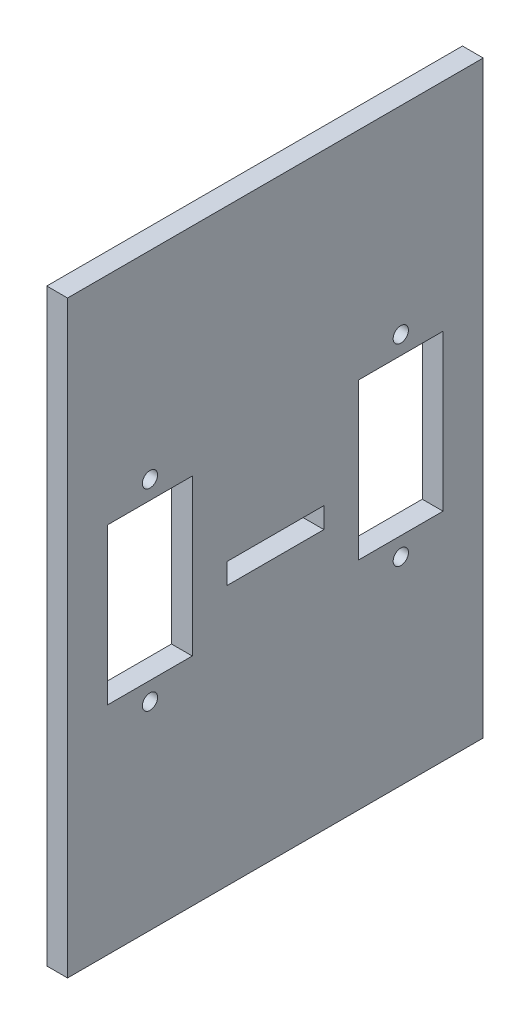
SolidWorks part; units mm, degrees
ref_plane "Front Plane" through (0, 0, 0) normal (0, 0, 1) x (1, 0, 0)
ref_plane "Top Plane" through (0, 0, 0) normal (0, 1, 0) x (1, 0, 0)
ref_plane "Right Plane" through (0, 0, 0) normal (1, 0, 0) x (0, 0, -1)
sketch "Sketch1" plane through (0, 0, 0) normal (1, 0, 0) x (0, 0, -1)
  line L0 (30, 0) -> (-30, 0) construction
  line L1 (-30, -42.5) -> (30, -42.5)
  line L2 (-30, -42.5) -> (-30, 42.5)
  line L3 (-30, 42.5) -> (30, 42.5)
  line L4 (30, -42.5) -> (30, 42.5)
  line L5 (-30, -42.5) -> (30, 42.5) construction
  line L6 (-30, 42.5) -> (30, -42.5) construction
  line L7 (0, 0) -> (12, 0) construction
  line L8 (24.2, -11.25) -> (12, -11.25)
  line L9 (24.2, -11.25) -> (24.2, 11.25)
  line L10 (24.2, 11.25) -> (12, 11.25)
  line L11 (12, -11.25) -> (12, 11.25)
  line L12 (18.1, 11.25) -> (18.1, 13.9) construction
  line L13 (0, 42.5) -> (0, -42.5) construction
  line L14 (-24.2, -11.25) -> (-12, -11.25)
  line L15 (-12, -11.25) -> (-12, 11.25)
  line L16 (-24.2, -11.25) -> (-24.2, 11.25)
  line L17 (-24.2, 11.25) -> (-12, 11.25)
  circle A0 centre (18.1, 13.9) radius 1.1
  circle A1 centre (18.1, -13.9) radius 1.1
  circle A2 centre (-18.1, -13.9) radius 1.1
  circle A3 centre (-18.1, 13.9) radius 1.1
  point P0 (0, 0)
  dimension "D6" = 2.2
  dimension "D1" = 22.5
  dimension "D2" = 12.2
  dimension "D3" = 85
  dimension "D4" = 60
  dimension "D5" = 12
  dimension "D7" = 2.65
extrude "Boss-Extrude1" add sketch "Sketch1" along normal blind 3
sketch "Sketch2" plane through (3, 0, 0) normal (1, 0, 0) x (0, 0, -1)
  line L0 (-12, 11.25) -> (12, 11.25) construction
  line L1 (0, 11.25) -> (0, -1.95) construction
  line L4 (-7, -1.95) -> (7, -1.95)
  line L5 (-7, -1.95) -> (-7, -4.95)
  line L6 (-7, -4.95) -> (7, -4.95)
  line L8 (7, -1.95) -> (7, -4.95)
  point P11 (0, -1.95)
  dimension "D1" = 13.2
  dimension "D2" = 14
  dimension "D3" = 3
extrude "Cut-Extrude1" cut sketch "Sketch2" against normal blind 3
